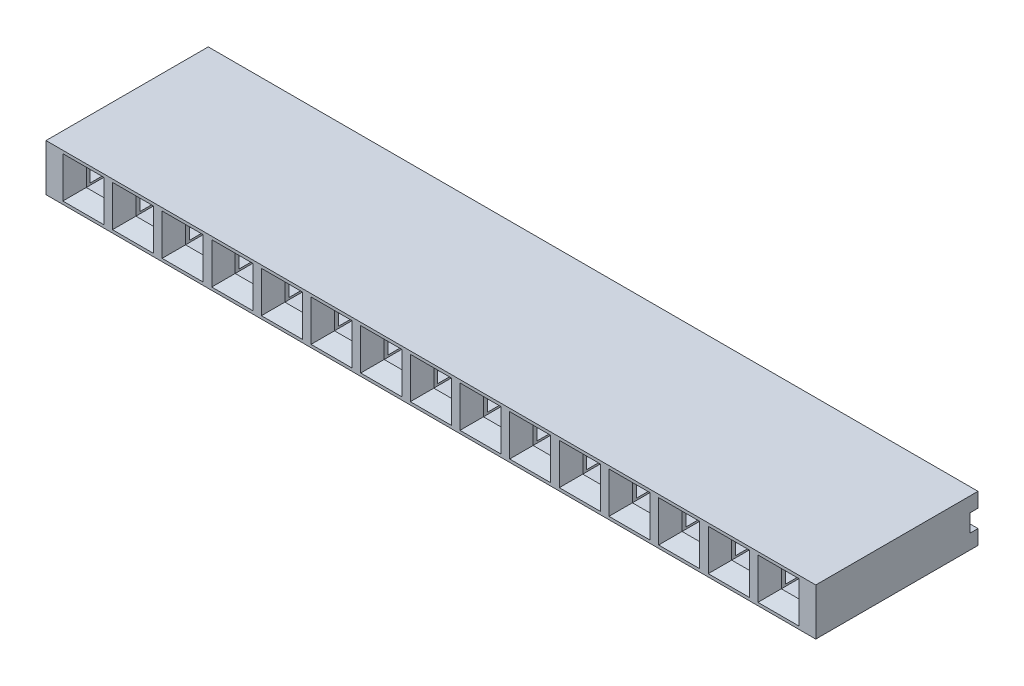
SolidWorks part; units mm, degrees
note: The reader was unsure of these and kept them because the rebuilt part matched: shared geometry of "Эскиз-БоковаяНакладка<2>".
other "Пластик"
ref_plane "Front Plane" through (0, 0, 0) normal (0, 0, 1) x (1, 0, 0)
ref_plane "Top Plane" through (0, 0, 0) normal (0, 1, 0) x (1, 0, 0)
ref_plane "Right Plane" through (0, 0, 0) normal (1, 0, 0) x (0, 0, -1)
sketch "Эскиз-ВнутреннееСечение" plane through (0, 0, 0) normal (0, 0, 1) x (1, 0, 0)
  line L0 (-1, 0.35) -> (-0.45, 0.35)
  line L1 (-1.27, -1.2) -> (1.27, -1.2)
  line L2 (-1.27, -1.2) -> (-1.27, 1.2)
  line L3 (-1.27, 1.2) -> (1.27, 1.2)
  line L4 (1.27, -1.2) -> (1.27, 1.2)
  line L5 (-1.27, -1.2) -> (1.27, 1.2) construction
  line L6 (-1.27, 1.2) -> (1.27, -1.2) construction
  line L8 (-1, -0.35) -> (-1, 0.35)
  line L9 (-0.45, 0.45) -> (0.45, 0.45)
  line L11 (0, 1.2) -> (0, -1.2) construction
  line L12 (0.45, 0.35) -> (0.45, 0.45)
  line L13 (-1.27, 0) -> (1.27, 0) construction
  line L14 (1, 0.35) -> (0.45, 0.35)
  line L15 (-0.45, 0.35) -> (-0.45, 0.45)
  line L16 (1, -0.35) -> (0.45, -0.35)
  line L17 (0.45, -0.35) -> (0.45, -0.45)
  line L18 (-0.45, -0.35) -> (-0.45, -0.45)
  line L19 (-1, -0.35) -> (-0.45, -0.35)
  line L20 (-0.45, -0.45) -> (0.45, -0.45)
  line L21 (1, -0.35) -> (1, 0.35)
  point P0 (0, 0)
  point P5 (0, 0)
  dimension "D1" = 2.4
  dimension "D2" = 2.54
  dimension "D3" = 1
  dimension "D4" = 0.35
  dimension "D5" = 0.1
  dimension "D7" = 0.55
extrude "Бобышка-ОтЦентраВверхВниз" add sketch "Эскиз-ВнутреннееСечение" against normal blind 0.4 and the other way blind 6.7 contours L8 L0 L15 L9 L12 L14 L21 L16 L17 L20 L18 L19
sketch "Эскиз-СамыйНиз" plane through (0, 0, -0.4) normal (0, 0, -1) x (-1, 0, 0)
  line L1 (1.27, 1.2) -> (1.27, -1.2) construction
  line L2 (-1.27, -1.2) -> (-1.27, 1.2) construction
  line L3 (0.45, -0.45) -> (-0.45, -0.45) construction
  line L4 (1.27, -1.2) -> (-1.27, -1.2)
  line L5 (1.27, -1.2) -> (1.27, -0.45)
  line L6 (1.27, -0.45) -> (-1.27, -0.45)
  line L7 (-1.27, -1.2) -> (-1.27, -0.45)
  line L9 (-1.27, 1.2) -> (1.27, 1.2)
  line L10 (-1.27, 1.2) -> (-1.27, 0.45)
  line L11 (-1.27, 0.45) -> (1.27, 0.45)
  line L12 (1.27, 1.2) -> (1.27, 0.45)
  line L13 (-0.45, 0.45) -> (0.45, 0.45) construction
  point P11 (0, 0)
extrude "Бобышка-СамыйНиз" add sketch "Эскиз-СамыйНиз" along normal blind 0.4
sketch "Эскиз-ВерхняяПеремычка" plane through (0, 0, 6.7) normal (0, 0, 1) x (1, 0, 0)
  line L1 (-1.27, 1.2) -> (1.27, 1.2)
  line L2 (-1.27, 1.2) -> (-1.27, -1.2)
  line L3 (-1.27, -1.2) -> (1.27, -1.2)
  line L4 (1.27, 1.2) -> (1.27, -1.2)
  line L5 (-0.45, -0.45) -> (0.45, -0.45)
  line L6 (-0.45, -0.45) -> (-0.45, 0.45)
  line L7 (-0.45, 0.45) -> (0.45, 0.45)
  line L8 (0.45, -0.45) -> (0.45, 0.45)
  line L9 (-0.45, -0.45) -> (0.45, 0.45) construction
  line L10 (-0.45, 0.45) -> (0.45, -0.45) construction
  point P4 (0, 0)
extrude "Бобышка-СамыйВерх" add sketch "Эскиз-ВерхняяПеремычка" along normal blind 0.8
chamfer "Фаска-СверхуВнутрь" distance 0.6 angle 45 4 edges at (0, -0.45, 7.5) (0.45, 0, 7.5) (0, 0.45, 7.5) (-0.45, 0, 7.5)
pattern_linear "Пластик_Массив" count 15 spacing 2.54 along (-1, 0, 0) of bodies 103
combine bodies "Соединить_Массив" operation type add bodies to combine 103 117 116 115 114 113 112 111 110 109 108 107 106 105 104
sketch "Эскиз-БоковаяНакладка" plane through (1.27, 0, 0) normal (1, 0, 0) x (0, 0, -1)
  line L1 (0.8, 1.2) -> (0.8, 0.45)
  line L2 (0.8, 0.45) -> (0.4, 0.45)
  line L3 (0.4, 0.45) -> (0.4, -0.45)
  line L4 (0.4, -0.45) -> (0.4, 0.45) construction
  line L5 (0.4, -0.45) -> (0.8, -0.45)
  line L6 (0.8, -0.45) -> (0.8, -1.2)
  line L7 (0.8, -1.2) -> (-7.5, -1.2)
  line L8 (-7.5, -1.2) -> (-7.5, 1.2)
  line L9 (-7.5, 1.2) -> (0.8, 1.2)
extrude "Бобышка-БоковаяНакладка1" add sketch "Эскиз-БоковаяНакладка" along normal blind 0.64 from surface at 0 starting at face at (1.27, 0, 1.375)
extrude "Бобышка-БоковаяНакладка2" add sketch "Эскиз-БоковаяНакладка<2>" against normal blind 0.64 from surface
sketch "Эскиз-БоковаяНакладка<2>" plane through (1.27, 0, 0) normal (1, 0, 0) x (0, 0, -1) same geometry as "Эскиз-БоковаяНакладка"
